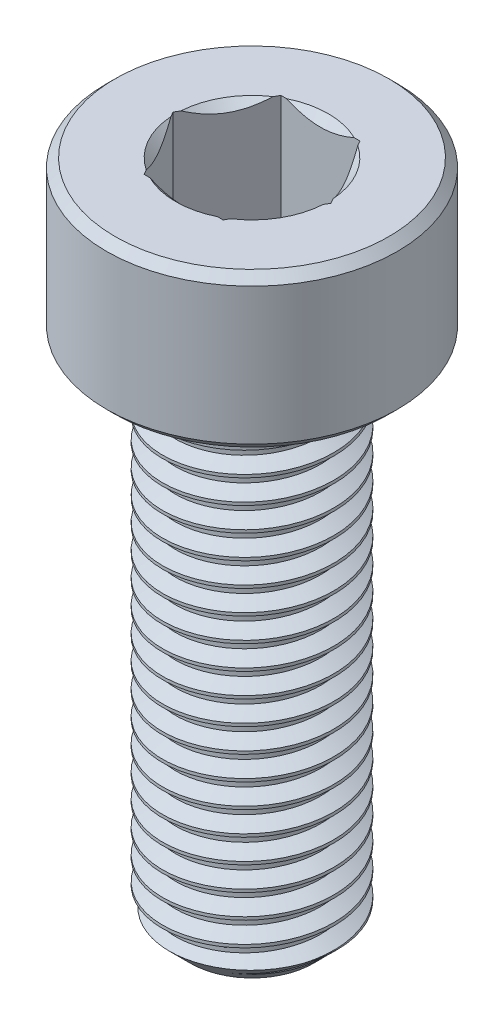
SolidWorks part; units mm, degrees
ref_plane "前视基准面" through (0, 0, 0) normal (0, 0, 1) x (1, 0, 0)
ref_plane "上视基准面" through (0, 0, 0) normal (0, 1, 0) x (1, 0, 0)
ref_plane "右视基准面" through (0, 0, 0) normal (1, 0, 0) x (0, 0, -1)
sketch "Sketch1" plane through (0, 0, 0) normal (0, 1, 0) x (1, 0, 0)
  circle A0 centre (0, 0) radius 2.5
  dimension "D1" = 5
extrude "Boss-Extrude2" add sketch "Sketch1" along normal blind 15
fillet "Chamfer1" radius 0.7 1 edges at (0, 0, 2.5) profile chamfer
thread "Thread2" pitch 0.7 method cut trim with end face yes profile "Thread Profile4" start angle 0, offset 0, length 40, pitch 0.7, diameter 5
ref_plane "Plane4" through (-2.5, 15, 0) normal (0, 0, 1) x (-1, 0, 0)
sketch "Thread Profile4" plane through (-2.5, 15, 0) normal (0, 0, 1) x (-1, 0, 0)
  line L0 (0, 0) -> (0, 0.7) construction
  line L11 (0, 0) -> (0, 0.6125)
  line L12 (0, 0.6125) -> (-0.3789, 0.3937)
  line L13 (-0.3789, 0.3937) -> (-0.3789, 0.2187)
  line L15 (-0.3789, 0.2187) -> (0, 0)
  line L17 (-0.3789, 0.3062) -> (0, 0.3062) construction
  point P2 (0, 0)
  dimension "Pitch" = 0.7
  dimension "Profile_Angle" = 60
  dimension "Profile_Land" = 0.175
  dimension "Profile_Height" = 0.3789
ref_plane "Plane5" through (0, 15, 0) normal (0, 1, 0) x (1, 0, 0)
sketch "Sketch11" plane through (0, 15, 0) normal (0, 1, 0) x (1, 0, 0)
  circle A0 centre (0, 0) radius 4.25
  dimension "D1" = 8.5
extrude "Boss-Extrude3" add sketch "Sketch11" along normal blind 4.5
ref_plane "Plane6" through (0, 19.5, 0) normal (0, 1, 0) x (1, 0, 0)
sketch "Sketch12" plane through (0, 19.5, 0) normal (0, 1, 0) x (1, 0, 0)
  circle A2 centre (0, 0) radius 2
  dimension "D1" = 4
extrude "Cut-Extrude4" cut sketch "Sketch12" against normal blind 3.5
fillet "Chamfer3" radius 0.23 1 edges at (0, 19.5, 2) profile chamfer
sketch "Sketch15" plane through (0, 19.5, 0) normal (0, 1, 0) x (1, 0, 0)
  line L1 (2.3094, 0) -> (1.1547, 2)
  line L2 (1.1547, 2) -> (-1.1547, 2)
  line L3 (-1.1547, 2) -> (-2.3094, 0)
  line L4 (-2.3094, 0) -> (-1.1547, -2)
  line L5 (-1.1547, -2) -> (1.1547, -2)
  line L6 (1.1547, -2) -> (2.3094, 0)
  circle A0 centre (0, 0) radius 2 construction
  dimension "D1" = 4
fillet "Chamfer4" radius 0.25 2 edges at (0, 19.5, 4.25) (0, 15, 4.25) profile chamfer
extrude "Cut-Extrude7" cut sketch "Sketch15" against normal blind 3.5
